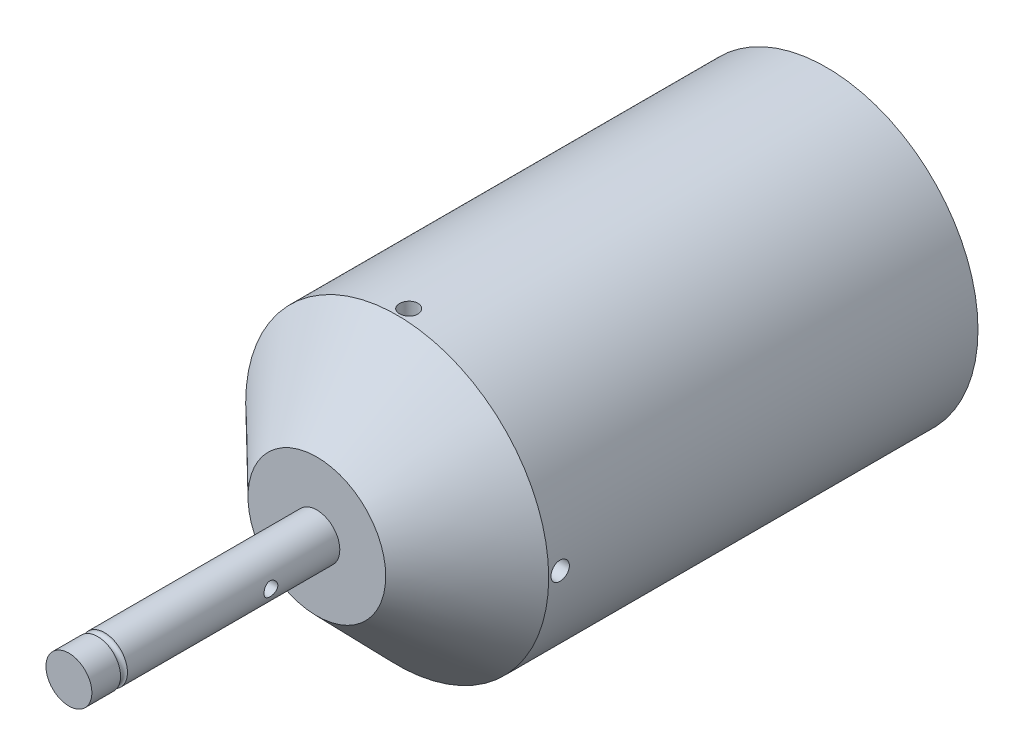
SolidWorks part; units mm, degrees
ref_plane "Front Plane" through (0, 0, 0) normal (0, 0, 1) x (1, 0, 0)
ref_plane "Top Plane" through (0, 0, 0) normal (0, 1, 0) x (1, 0, 0)
ref_plane "Right Plane" through (0, 0, 0) normal (1, 0, 0) x (0, 0, -1)
sketch "Sketch1" plane through (0, 0, 0) normal (0, 0, 1) x (1, 0, 0)
  circle A0 centre (0, 0) radius 33
  dimension "D1" = 66
extrude "Boss-Extrude1" add sketch "Sketch1" against normal mid plane 93.5
sketch "Sketch10" plane through (0, 0, 0) normal (1, 0, 0) x (0, 0, -1)
  line L0 (-64.25, 0) -> (-64.25, 15)
  line L1 (-46.75, 33) -> (-64.25, 15)
  line L2 (-1000, 0) -> (49000, 0) construction
  line L3 (-64.25, 0) -> (-46.75, 0)
  line L4 (-46.75, 0) -> (-46.75, 33)
  line L5 (46.75, -33) -> (46.75, 33) construction
  point P3 (-64.25, 0)
  dimension "D1" = 15
  dimension "D2" = 111
revolve "Revolve1" add sketch "Sketch10" angle 360 about L2
ref_plane "Plane1" through (0, 33, 0) normal (0, 1, 0) x (1, 0, 0)
sketch "Sketch11" plane through (-33, 33, 0) normal (0, -1, 0) x (0, 0, -1)
  line L0 (-64.25, 33) -> (46.75, 33) construction
  line L2 (-64.25, 48) -> (-64.25, 18) construction
  line L3 (46.75, 0) -> (46.75, 66) construction
  circle A0 centre (-44.25, 33) radius 2
  point P5 (0, 0)
  dimension "D1" = 4
  dimension "D2" = 91
extrude "Cut-Extrude1" cut sketch "Sketch11" along normal blind 5 and the other way through all
pattern_circular "CirPattern1" count 4 over 360 about axis through (0, 0, 46.75) along (0, 0, 1) of "Cut-Extrude1"
sketch "Sketch12" plane through (0, 0, 64.25) normal (0, 0, 1) x (1, 0, 0)
  circle A0 centre (0, 0) radius 5
  dimension "D1" = 10
extrude "Boss-Extrude5" add sketch "Sketch12" along normal blind 54
sketch "Sketch13" plane through (0, 0, 0) normal (1, 0, 0) x (0, 0, -1)
  line L0 (-118.25, 5) -> (-118.25, -5) construction
  circle A0 centre (-79.25, 0) radius 1.5
  dimension "D1" = 3
  dimension "D2" = 39
extrude "Cut-Extrude2" cut sketch "Sketch13" against normal through all both and the other way through all
sketch "Sketch14" plane through (0, 0, 0) normal (1, 0, 0) x (0, 0, -1)
  line L0 (-64.25, 5) -> (-118.25, 5) construction
  line L1 (-118.25, 5) -> (-118.25, -5) construction
  circle A0 centre (-111.25, 5) radius 0.75
  dimension "D1" = 1.5
  dimension "D2" = 7
revolve "Cut-Revolve1" cut sketch "Sketch14" angle 360 about axis through (0, 0, 118.25) along (0, 0, -1)
